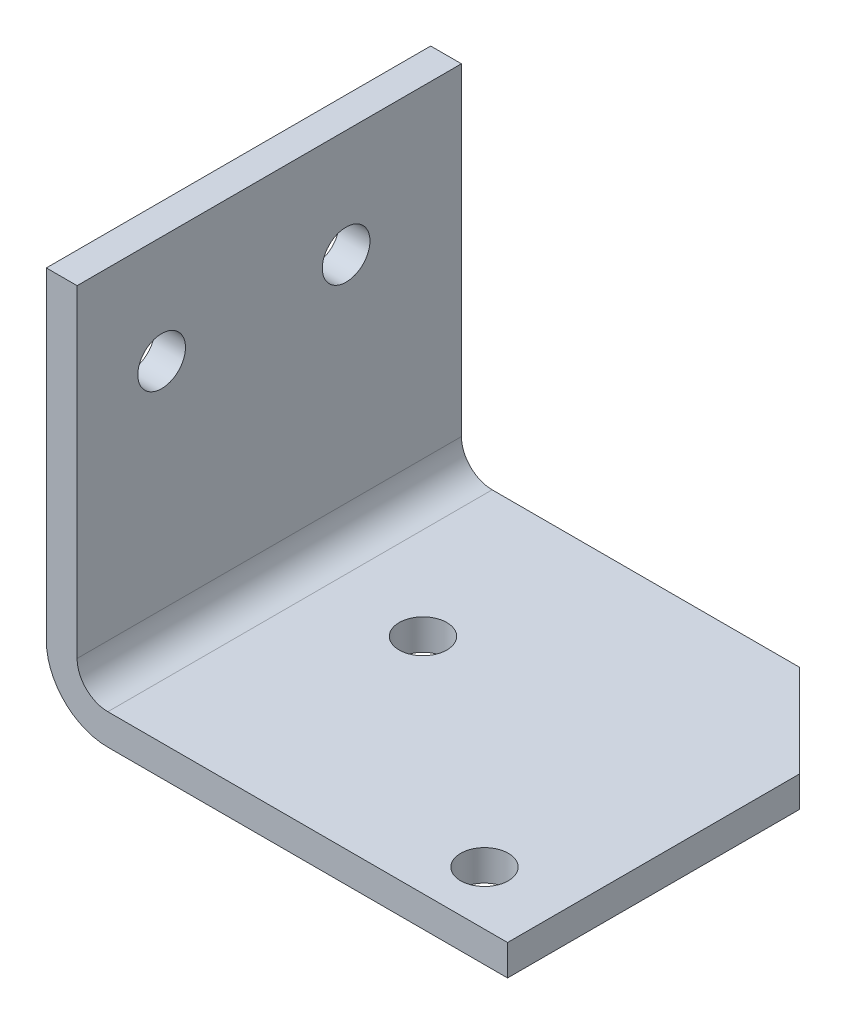
SolidWorks part; units mm, degrees
material "6061 Alloy"
ref_plane "Спереди" through (0, 0, 0) normal (0, 0, 1) x (1, 0, 0)
ref_plane "Сверху" through (0, 0, 0) normal (0, 1, 0) x (1, 0, 0)
ref_plane "Справа" through (0, 0, 0) normal (1, 0, 0) x (0, 0, -1)
sketch "Sketch1" plane through (0, 0, 0) normal (0, 0, 1) x (1, 0, 0)
  line L0 (0, 0) -> (30, 0)
  line L1 (30, 0) -> (30, 2)
  line L2 (30, 2) -> (2, 2)
  line L3 (2, 2) -> (2, 25)
  line L4 (2, 25) -> (0, 25)
  line L5 (0, 25) -> (0, 0)
  dimension "D1" = 30
  dimension "D2" = 25
  dimension "D3" = 2
  dimension "D4" = 2
extrude "Boss-Extrude1" add sketch "Sketch1" along normal blind 25
sketch "Sketch2" plane through (0, 0, 0) normal (-1, 0, 0) x (0, 0, 1)
  line L0 (25, 25) -> (25, 0) construction
  line L2 (25, 0) -> (0, 0) construction
  circle A0 centre (19.5, 18) radius 1.55
  circle A1 centre (7.5, 18) radius 1.55
  dimension "D5" = 3.1
  dimension "D1" = 12
  dimension "D2" = 5.5
  dimension "D3" = 18
extrude "Cut-Extrude1" cut sketch "Sketch2" against normal up to surface (2 mm away) up to face at (2, 13.5, 12.5)
sketch "Sketch4" plane through (0, 0, 0) normal (0, -1, 0) x (1, 0, 0)
  line L0 (0, 25) -> (0, 0) construction
  line L1 (0, 0) -> (30, 0) construction
  circle A0 centre (10, 10.5) radius 1.55
  circle A1 centre (25, 21.5) radius 1.55
  dimension "D5" = 3.1
  dimension "D6" = 3.1
  dimension "D1" = 21.5
  dimension "D2" = 10.5
  dimension "D3" = 10
  dimension "D4" = 15
extrude "Cut-Extrude3" cut sketch "Sketch4" against normal through all
chamfer "Chamfer2" distance 6 angle 45 1 edges at (30, 1, 0)
fillet "Fillet1" radius 2 1 edges at (2, 2, 12.5)
fillet "Fillet2" radius 4 1 edges at (0, 0, 12.5)
